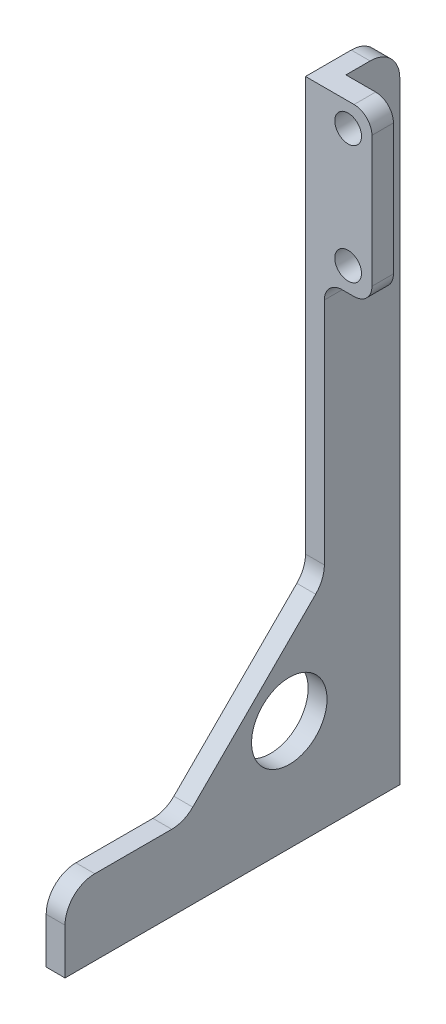
SolidWorks part; units mm, degrees
ref_plane "Front Plane" through (0, 0, 0) normal (0, 0, 1) x (1, 0, 0)
ref_plane "Top Plane" through (0, 0, 0) normal (0, 1, 0) x (1, 0, 0)
ref_plane "Right Plane" through (0, 0, 0) normal (1, 0, 0) x (0, 0, -1)
sketch "Sketch2" plane through (0, 0, 0) normal (1, 0, 0) x (0, 0, -1)
  line L0 (0, 0) -> (0, -101.6552) construction
  line L1 (0, -101.6552) -> (-50, -101.6552) construction
  line L3 (-50, -95.3052) -> (-6.35, -95.3052) construction
  line L4 (-6.35, -95.3052) -> (-6.35, 0) construction
  line L5 (-6.35, 0) -> (6.35, 0)
  line L6 (6.35, 0) -> (6.35, -108.0052)
  line L7 (6.35, -108.0052) -> (-50, -108.0052)
  line L9 (-50, -108.0052) -> (-50, -95.3052)
  line L10 (-29.9674, -95.3052) -> (-6.35, -71.6879)
  line L11 (-50, -95.3052) -> (-29.9674, -95.3052)
  line L12 (-6.35, -71.6879) -> (-6.35, 0)
  line L13 (-18.1587, -83.4966) -> (-6.35, -95.3052) construction
  circle A0 centre (-12.2543, -89.4009) radius 6.35
  circle A1 centre (-12.2543, -89.4009) radius 8.35 construction
  point P16 (5.4652, -107.1205)
  point P17 (-6.35, -64.8278)
  point P18 (0, 0)
  dimension "D4" = 2
  dimension "D5" = 12.7
  dimension "D6" = 12.7
  dimension "D1" = 101.6552
  dimension "D2" = 50
  dimension "D3" = 135
extrude "Boss-Extrude1" add sketch "Sketch2" against normal blind 3.175
fillet "Fillet1" radius 5 4 edges at (-1.5875, 0, -6.35) (-1.5875, -95.3052, 50) (-1.5875, -95.3052, 29.9674) (-1.5875, -71.6879, 6.35)
sketch "Sketch3" plane through (0, 0, 0) normal (1, 0, 0) x (0, 0, -1)
  line L0 (-6.35, 0) -> (-6.35, -28)
  line L1 (-6.35, -28) -> (-2.7202, -28)
  line L2 (-2.7202, -28) -> (-2.7202, 0)
  line L3 (-2.7202, 0) -> (-6.35, 0)
  dimension "D1" = 3.6298
  dimension "D2" = 28
extrude "Boss-Extrude2" add sketch "Sketch3" along normal blind 8
ref_plane "Plane1" through (0, 0, 2.7202) normal (0, 0, -1) x (-1, 0, 0)
sketch "Sketch4" plane through (0, 0, 2.7202) normal (0, 0, -1) x (-1, 0, 0)
  line L0 (0, -28) -> (-8, 0) construction
  line L1 (-4, -24) -> (-4, -4) construction
  line L4 (0, -28) -> (0, 0)
  line L5 (0, 0) -> (-8, 0)
  line L6 (-8, 0) -> (-8, -28)
  line L7 (-8, -28) -> (0, -28)
  line L8 (0, -28) -> (0, 0)
  line L9 (0, 0) -> (-8, 0)
  line L10 (-8, 0) -> (-8, -28)
  line L11 (-8, -28) -> (0, -28)
  circle A0 centre (-4, -24) radius 2.25
  circle A1 centre (-4, -4) radius 2.25
  point P6 (-4, -14)
  point P7 (-4, -14)
  dimension "D2" = 4.5
  dimension "D3" = 20
  dimension "D1" = 0
extrude "Cut-Extrude1" cut sketch "Sketch4" against normal up to surface (3.6298 mm away) contours A0 | A1 up to face at (1.6083, -32.5389, 6.35)
fillet "Fillet2" radius 3 3 edges at (8, 0, 4.5351) (8, -28, 4.5351) (0, -28, 4.5351)
